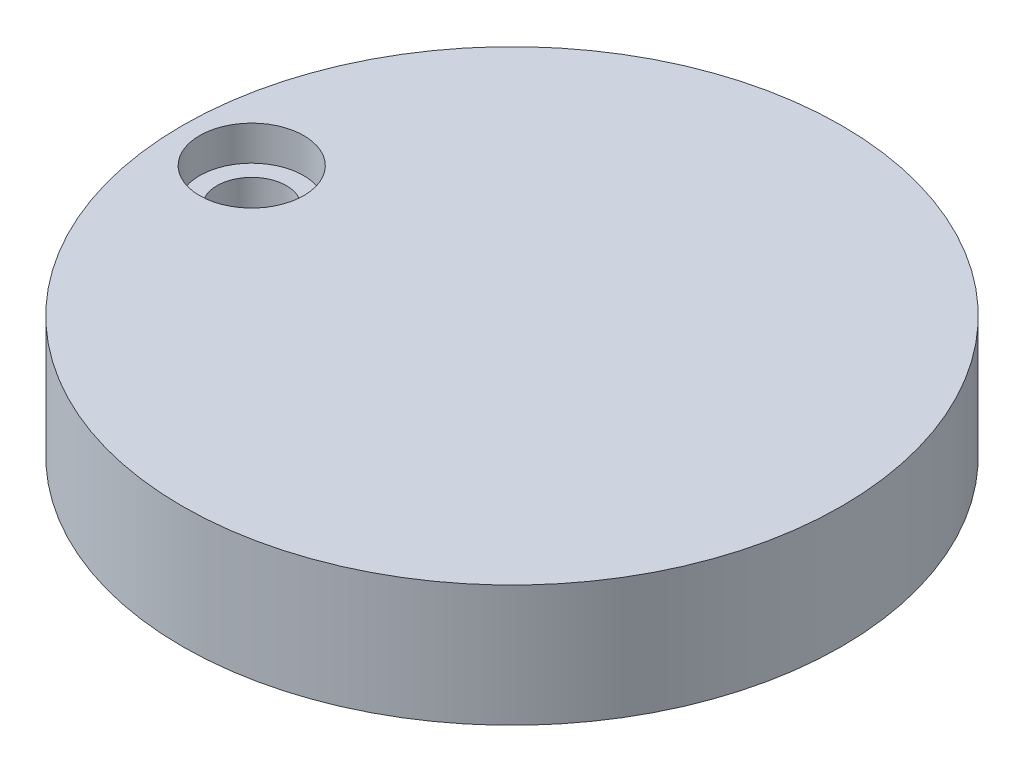
SolidWorks part; units mm, degrees
ref_plane "Planta" through (0, 0, 0) normal (0, 0, 1) x (1, 0, 0)
ref_plane "Alzado" through (0, 0, 0) normal (0, 1, 0) x (1, 0, 0)
ref_plane "Vista lateral" through (0, 0, 0) normal (1, 0, 0) x (0, 0, -1)
sketch "Croquis2" plane through (0, 0, 0) normal (0, 1, 0) x (1, 0, 0)
  circle A0 centre (0, 0) radius 19
  circle A1 centre (0, 0) radius 6
  circle A2 centre (-15, 0) radius 2
  point P4 (-15, 0)
  dimension "D1" = 38
  dimension "D2" = 12
  dimension "D4" = 4
  dimension "D3" = 15
extrude "Saliente-Extruir1" add sketch "Croquis2" along normal blind 7 contours A0
extrude "Saliente-Extruir2" add sketch "Croquis2<4>" against normal blind 8 contours A1
sketch "Croquis2<4>" plane through (0, 0, 0) normal (0, 1, 0) x (1, 0, 0) same geometry as "Croquis2"
extrude "Cortar-Extruir2" cut sketch "Croquis2<5>" along normal through all contours A2
sketch "Croquis2<5>" plane through (0, 0, 0) normal (0, 1, 0) x (1, 0, 0) same geometry as "Croquis2"
sketch "Croquis5" plane through (0, 7, 0) normal (0, 1, 0) x (1, 0, 0)
  circle A0 centre (-15, 0) radius 3
  dimension "D1" = 6
extrude "Cortar-Extruir3" cut sketch "Croquis5" against normal blind 2
